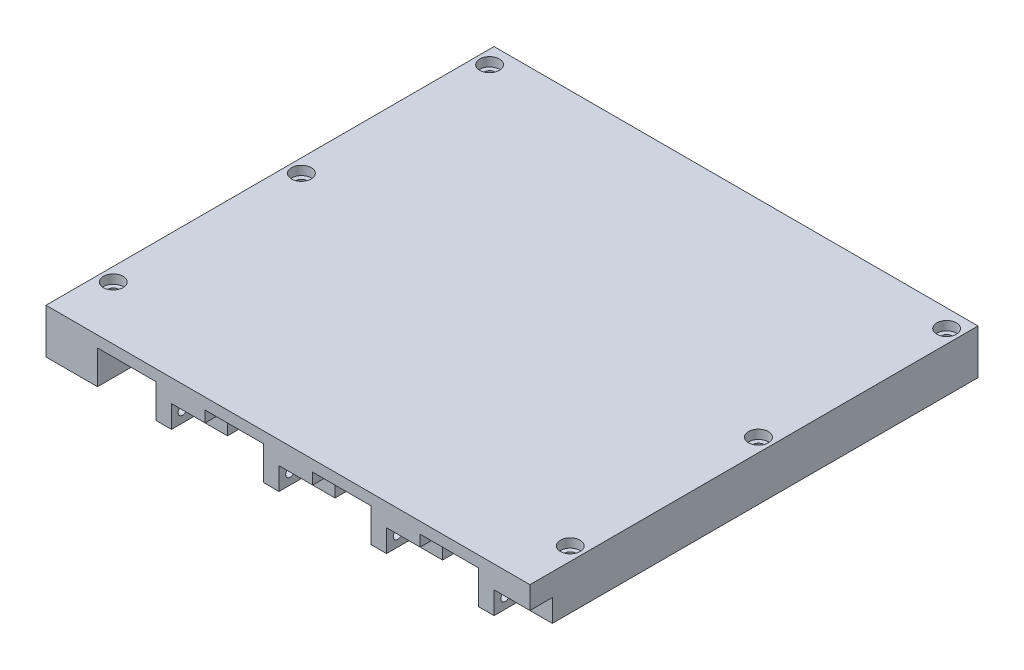
SolidWorks part; units mm, degrees
ref_plane "Front Plane" through (0, 0, 0) normal (0, 0, 1) x (1, 0, 0)
ref_plane "Top Plane" through (0, 0, 0) normal (0, 1, 0) x (1, 0, 0)
ref_plane "Right Plane" through (0, 0, 0) normal (1, 0, 0) x (0, 0, -1)
sketch "Sketch1" plane through (0, 0, 0) normal (0, 1, 0) x (1, 0, 0)
  line L1 (54, -50) -> (-54, -50)
  line L2 (54, -50) -> (54, 50)
  line L3 (54, 50) -> (-54, 50)
  line L4 (-54, -50) -> (-54, 50)
  line L5 (54, -50) -> (-54, 50) construction
  line L6 (54, 50) -> (-54, -50) construction
  point P0 (0, 0)
  dimension "D1" = 108
  dimension "D2" = 100
extrude "Boss-Extrude1" add sketch "Sketch1" along normal blind 10 contours L3 L1 | L3 L4 L1 | L3 L1 L2 region at (0, 0, 0)
sketch "Sketch2" plane through (0, 0, 50) normal (0, 0, 1) x (1, 0, 0)
  line L0 (-60, 0) -> (60, 0) construction
  line L4 (-29.5, -7.5) -> (-42.5, -7.5)
  line L5 (-29.5, -7.5) -> (-29.5, 7.5)
  line L6 (-29.5, 7.5) -> (-42.5, 7.5)
  line L7 (-42.5, -7.5) -> (-42.5, 7.5)
  line L8 (-29.5, -7.5) -> (-42.5, 7.5) construction
  line L9 (-29.5, 7.5) -> (-42.5, -7.5) construction
  line L10 (-5.5, -7.5) -> (-18.5, -7.5)
  line L11 (-5.5, -7.5) -> (-5.5, 7.5)
  line L12 (-5.5, 7.5) -> (-18.5, 7.5)
  line L13 (-18.5, -7.5) -> (-18.5, 7.5)
  line L14 (-5.5, -7.5) -> (-18.5, 7.5) construction
  line L15 (-5.5, 7.5) -> (-18.5, -7.5) construction
  line L16 (18.5, -7.5) -> (5.5, -7.5)
  line L17 (18.5, -7.5) -> (18.5, 7.5)
  line L18 (18.5, 7.5) -> (5.5, 7.5)
  line L19 (5.5, -7.5) -> (5.5, 7.5)
  line L20 (18.5, -7.5) -> (5.5, 7.5) construction
  line L21 (18.5, 7.5) -> (5.5, -7.5) construction
  line L22 (42.5, -7.5) -> (29.5, -7.5)
  line L23 (42.5, -7.5) -> (42.5, 7.5)
  line L24 (42.5, 7.5) -> (29.5, 7.5)
  line L25 (29.5, -7.5) -> (29.5, 7.5)
  line L26 (42.5, -7.5) -> (29.5, 7.5) construction
  line L27 (42.5, 7.5) -> (29.5, -7.5) construction
  line L29 (54, 0) -> (-54, 0) construction
  point P7 (-36, 0)
  point P8 (-12, 0)
  point P9 (12, 0)
  point P10 (36, 0)
  point P11 (-36, 0)
  point P16 (-12, 0)
  point P21 (12, 0)
  point P26 (36, 0)
  point P33 (0, 0)
  dimension "D1" = 120
  dimension "D3" = 13
  dimension "D4" = 15
extrude "Cut-Extrude1" cut sketch "Sketch2" against normal blind 35
sketch "Sketch3" plane through (0, 0, 50) normal (0, 0, 1) x (1, 0, 0)
  line L1 (-18.5, 0) -> (-26, 0)
  line L2 (-18.5, 0) -> (-18.5, 5)
  line L3 (-18.5, 5) -> (-26, 5)
  line L4 (-26, 0) -> (-26, 5)
  line L5 (5.5, 0) -> (-2, 0)
  line L6 (5.5, 0) -> (5.5, 5)
  line L7 (5.5, 5) -> (-2, 5)
  line L8 (-2, 0) -> (-2, 5)
  line L9 (29.5, 0) -> (22, 0)
  line L10 (29.5, 0) -> (29.5, 5)
  line L11 (29.5, 5) -> (22, 5)
  line L12 (22, 0) -> (22, 5)
  line L13 (46, 0) -> (56, 0)
  line L14 (46, 0) -> (46, 5)
  line L15 (46, 5) -> (56, 5)
  line L16 (56, 0) -> (56, 5)
  line L17 (54, 0) -> (42.5, 0) construction
  line L18 (5.5, 7.5) -> (5.5, 0) construction
  line L19 (5.5, 0) -> (-5.5, 0) construction
  line L21 (-29.5, 0) -> (-29.5, 7.5) construction
  line L22 (-5.5, 0) -> (-5.5, 7.5) construction
  line L23 (42.5, 0) -> (42.5, 7.5) construction
  line L24 (18.5, 0) -> (18.5, 7.5) construction
  line L25 (-18.5, 0) -> (-5.5, 0) construction
  line L26 (-18.5, 7.5) -> (-18.5, 0) construction
  dimension "D1" = 3.5
  dimension "D2" = 3.5
  dimension "D3" = 3.5
  dimension "D4" = 3.5
  dimension "D5" = 5
  dimension "D6" = 5
  dimension "D7" = 5
  dimension "D8" = 5
  dimension "D9" = 10
extrude "Cut-Extrude2" cut sketch "Sketch3" against normal blind 5
sketch "Sketch4" plane through (46, 0, 0) normal (1, 0, 0) x (0, 0, -1)
  line L0 (-45, 0) -> (-50, 0) construction
  line L2 (-50, 10) -> (-50, 5) construction
  circle A0 centre (-47.5, 2.5) radius 1
  dimension "D1" = 2
  dimension "D2" = 2.5
  dimension "D3" = 2.5
extrude "Cut-Extrude3" cut sketch "Sketch4" against normal up to surface (75.5 mm away) up to face at (-29.5, 3.75, 32.5)
hole_wizard "CBORE for M2 SHCS1" positions "Sketch7" profile "Sketch8" counterbore size "M2" standard "ANSI Metric"
sketch "Sketch7" plane through (-676.2935, 10, -1323.2827) normal (0, 1, 0) x (1, 0, 0)
  line L3 (625.2935, -1277.2827) -> (625.2935, -1361.2827) construction
  line L5 (727.2935, -1277.2827) -> (727.2935, -1361.2827) construction
  circle A0 centre (727.2935, -1277.2827) radius 2.243
  circle A1 centre (727.2935, -1361.2827) radius 2.2384
  circle A3 centre (625.2935, -1277.2827) radius 2.3325
  circle A4 centre (625.2935, -1361.2827) radius 1.7576
  circle A5 centre (625.2935, -1319.2827) radius 1.8624
  circle A6 centre (727.2935, -1319.2827) radius 2.0271
  point P1 (727.2935, -1277.2827)
  point P8 (727.2935, -1361.2827)
  point P15 (625.2935, -1277.2827)
  point P17 (625.2935, -1361.2827)
  point P19 (625.2935, -1319.2827)
  point P27 (727.2935, -1319.2827)
sketch "Sketch8" plane through (51, 10, -46) normal (1, 0, 0) x (0, 0, 1)
  line L0 (0, 0) -> (0, 20.721)
  line L1 (0, 20.721) -> (1.2, 20)
  line L2 (1.2, 20) -> (1.2, 2)
  line L3 (1.2, 2) -> (2.2, 2)
  line L4 (2.2, 2) -> (2.2, 0)
  line L5 (2.2, 0) -> (0, 0)
  line L6 (0, 20.721) -> (-1.2, 20) construction
  line L7 (0, -6.35) -> (0, 107.95) construction
  dimension "Hole Dia." = 2.4
  dimension "Hole Depth" = 20
  dimension "C'Bore Dia." = 4.4
  dimension "C'Bore Depth" = 2
  dimension "Drill Angle" = 118
